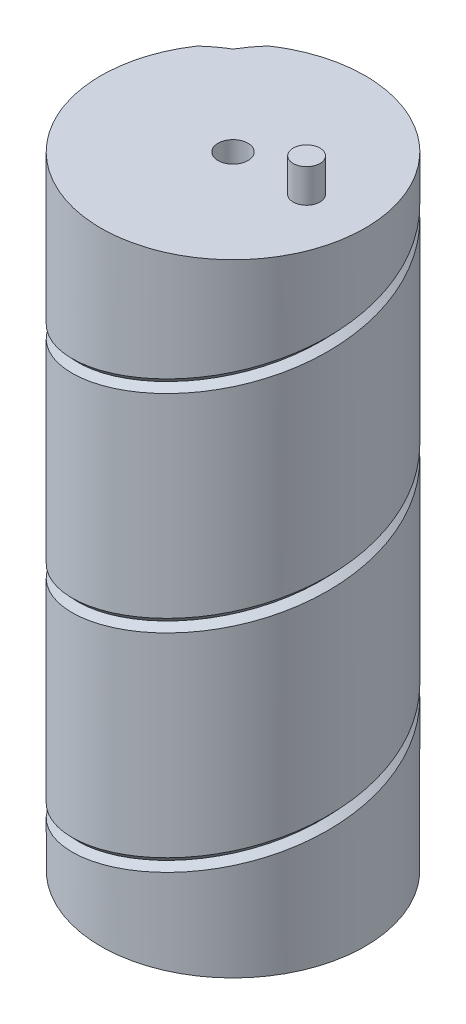
SolidWorks part; units mm, degrees
ref_plane "Front Plane" through (0, 0, 0) normal (0, 0, 1) x (1, 0, 0)
ref_plane "Top Plane" through (0, 0, 0) normal (0, 1, 0) x (1, 0, 0)
ref_plane "Right Plane" through (0, 0, 0) normal (1, 0, 0) x (0, 0, -1)
sketch "Sketch1" plane through (0, 0, 0) normal (0, 1, 0) x (1, 0, 0)
  line L0 (-19.75, 0) -> (19.75, 0) construction
  circle A0 centre (0, 0) radius 19.75
  dimension "D1" = 39.5
curve "Helix - Antenna Guide" pitch 31 height 93 radius 19.75 centre (0, 0, 0) axis (0, 1, 0) start towards (0, 0, 1)
extrude "Extrude - Main Body" add sketch "Sketch1<2>" along normal blind 93
sketch "Sketch1<2>" plane through (0, 0, 0) normal (0, 1, 0) x (1, 0, 0) same geometry as "Sketch1"
ref_point "Point2"
ref_point "Point1"
ref_plane "Plane1" through (-13.9654, 0, -13.9654) normal (-0.686, 0.2424, 0.686) x (-0.7276, -0.2285, -0.6468)
sketch "Sketch15" plane through (-13.9654, 0, -13.9654) normal (-0.686, 0.2424, 0.686) x (-0.7276, -0.2285, -0.6468)
  line L4 (0, 0) -> (0.2165, 0.8934)
  line L5 (0.2165, 0.8934) -> (-0.8934, 0.2165)
  line L8 (0, 0) -> (-0.2165, -0.8934)
  line L9 (-0.2165, -0.8934) -> (-0.8934, 0.2165)
  point P7 (-0.5549, -0.3384)
  dimension "D1" = 0.65
  dimension "D2" = 90
sweep "Cut - Antenna Wire Guide" cut profiles "Sketch15" path "Helix - Antenna Guide" align with end faces yes
sketch "Sketch23" plane through (0, 0, 0) normal (0, -1, 0) x (1, 0, 0)
  line L0 (-13.3154, -13.3154) -> (-8.3849, -14.1466)
  line L1 (-9.335, -17.4046) -> (-10.0329, -12.4535)
  arc A0 (-11.0473, -16.3713) -> (-16.3713, -11.0473) centre (0, 0) ccw construction
  arc A1 (-10.0329, -12.4535) -> (-8.3849, -14.1466) centre (-8.0525, -12.1744) cw
  arc A2 (-9.335, -17.4046) -> (-13.3154, -13.3154) centre (-14.1184, -18.0788) cw
  dimension "D2" = 2
  dimension "D1" = 2
  dimension "D3" = 5
  dimension "D4" = 5
ref_plane "Plane - Anchor Loop Exit" through (-9.335, 0, -17.4046) normal (-0.1396, 0, 0.9902) x (0.9902, 0, 0.1396)
ref_plane "Plane - Anchor Loop Peg" through (-10.0329, 0, -12.4535) normal (-0.1396, 0, 0.9902) x (0.9902, 0, 0.1396)
sketch "Sketch28" plane through (0, 93, 0) normal (0, 1, 0) x (1, 0, 0)
  circle A0 centre (11, 0) radius 2
  point P0 (0, 0)
  dimension "D1" = 4
  dimension "D2" = 11
extrude "Extruded Peg" add sketch "Sketch28" along normal blind 5
hole_wizard "Hole for Threaded Rod" positions "Sketch29" profile "Sketch30" hole size "#8" standard "ANSI Inch" end condition through all
sketch "Sketch29" plane through (0, 93, 0) normal (0, 1, 0) x (1, 0, 0)
  point P0 (0, 0)
sketch "Sketch30" plane through (0, 93, 0) normal (1, 0, 0) x (0, 0, 1)
  line L0 (0, 0) -> (0, 94.4693)
  line L1 (0, 94.4693) -> (2.2479, 94.4693)
  line L2 (2.2479, 94.4693) -> (2.2479, 0)
  line L5 (2.2479, 0) -> (0, 0)
  line L11 (0, -6.35) -> (0, 107.95) construction
  dimension "Thru Hole Dia." = 4.4958
  dimension "Thru Hole Depth" = 94.4693
sketch "Sketch31" plane through (0, 0, 0) normal (0, -1, 0) x (1, 0, 0)
  circle A0 centre (11, 0) radius 2.25
  dimension "D1" = 4.5
  dimension "D2" = 11
extrude "Cut Peg" cut sketch "Sketch31" against normal blind 5.5
sketch "anchor loop" plane through (0, 93, 0) normal (0, 1, 0) x (1, 0, 0)
  line L0 (-12.5371, 6.4669) -> (-12.5371, 10.4669) construction
  line L1 (-14.5371, 8.4669) -> (-10.5371, 8.4669) construction
  line L2 (-12.5371, 10.4669) -> (-17.4078, 9.3369)
  line L3 (-14.5371, 8.4669) -> (-13.3154, 13.3154)
  arc A0 (-13.3154, 13.3154) -> (-17.4078, 9.3369) centre (-18.0788, 14.1212) ccw
  arc A1 (-16.3744, 11.0494) -> (-11.0494, 16.3744) centre (0, 0) ccw construction
  arc A2 (-14.5371, 8.4669) -> (-12.5371, 10.4669) centre (-12.5371, 8.4669) ccw
  dimension "D1" = 2
  dimension "D2" = 4
  dimension "D5" = 4.8311
  dimension "D3" = 5
  dimension "D4" = 5
ref_plane "plane- anchor loop exit" through (-17.4078, 93, -9.3369) normal (0.9741, 0, -0.226) x (-0.226, 0, -0.9741)
ref_plane "Plane3" through (-12.5371, 93, -10.4669) normal (0.9741, 0, -0.226) x (-0.226, 0, -0.9741)
equation "\"pegD\"=10"
equation "\"pegHoleD\"=0.5"
equation "\"pegHoleOffset\"=0.5"
